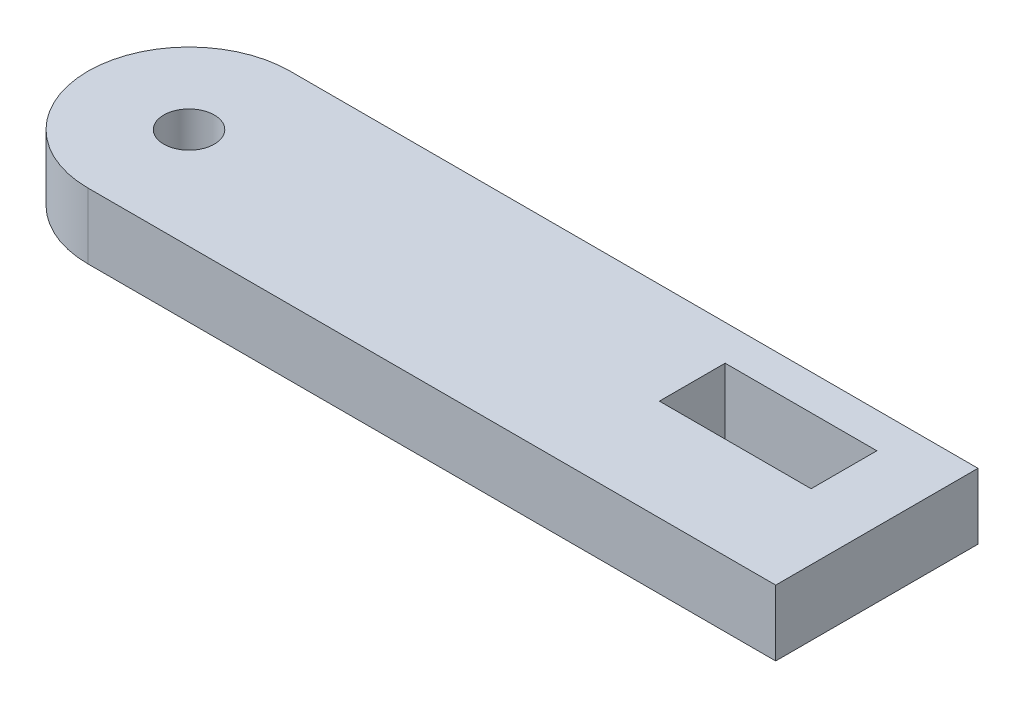
SolidWorks part; units mm, degrees
ref_plane "Front Plane" through (0, 0, 0) normal (0, 0, 1) x (1, 0, 0)
ref_plane "Top Plane" through (0, 0, 0) normal (0, 1, 0) x (1, 0, 0)
ref_plane "Right Plane" through (0, 0, 0) normal (1, 0, 0) x (0, 0, -1)
sketch "Sketch1" plane through (0, 0, 0) normal (0, 1, 0) x (1, 0, 0)
  line L1 (0, 0) -> (78, 0)
  line L2 (0, 0) -> (0, 20)
  line L3 (0, 20) -> (78, 20)
  line L4 (78, 0) -> (78, 20)
  dimension "D1" = 78
  dimension "D2" = 20
extrude "Boss-Extrude1" add sketch "Sketch1" along normal blind 6.5
sketch "Sketch2" plane through (0, 6.5, 0) normal (0, 1, 0) x (1, 0, 0)
  line L0 (0, 0) -> (78, 0) construction
  line L1 (0, 20) -> (0, 0) construction
  circle A0 centre (10, 10) radius 2.5
  dimension "D1" = 5
  dimension "D2" = 10
  dimension "D3" = 10
extrude "Cut-Extrude1" cut sketch "Sketch2" against normal through all
sketch "Sketch3" plane through (0, 6.5, 0) normal (0, 1, 0) x (1, 0, 0)
  line L0 (0, 0) -> (78, 0) construction
  line L1 (71.5, 16.5) -> (56.5, 16.5)
  line L2 (71.5, 16.5) -> (71.5, 10)
  line L3 (71.5, 10) -> (56.5, 10)
  line L4 (56.5, 16.5) -> (56.5, 10)
  line L5 (78, 0) -> (78, 20) construction
  dimension "D1" = 6.5
  dimension "D2" = 10
  dimension "D3" = 6.5
  dimension "D4" = 15
extrude "Cut-Extrude2" cut sketch "Sketch3" against normal through all
fillet "Fillet1" radius 10 2 edges at (0, 3.25, 0) (0, 3.25, -20)
